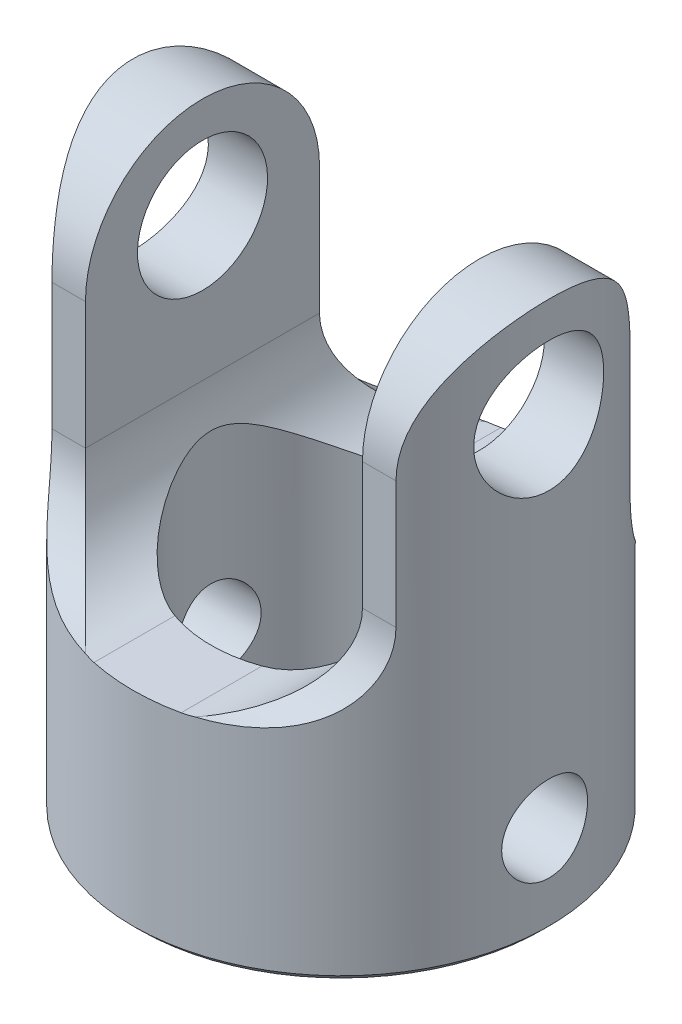
SolidWorks part; units mm, degrees
material "AISI 1045 Steel, cold drawn"
ref_plane "Front Plane" through (0, 0, 0) normal (0, 0, 1) x (1, 0, 0)
ref_plane "Top Plane" through (0, 0, 0) normal (0, 1, 0) x (1, 0, 0)
ref_plane "Right Plane" through (0, 0, 0) normal (1, 0, 0) x (0, 0, -1)
sketch "Sketch1" plane through (0, 0, 0) normal (0, 1, 0) x (1, 0, 0)
  circle A0 centre (0, 0) radius 8
  circle A1 centre (0, 0) radius 5
  dimension "D1" = 16
  dimension "D2" = 10
extrude "Boss-Extrude2" add sketch "Sketch1" along normal mid plane 25
sketch "Sketch3" plane through (0, 0, 0) normal (0, 0, 1) x (1, 0, 0)
  line L1 (-5.325, 13.5) -> (5.325, 13.5)
  line L2 (-5.325, 13.5) -> (-5.325, -4.4)
  line L3 (-5.325, -4.4) -> (5.325, -4.4)
  line L4 (5.325, 13.5) -> (5.325, -4.4)
  line L5 (-5.325, 13.5) -> (5.325, -4.4) construction
  line L6 (-5.325, -4.4) -> (5.325, 13.5) construction
  line L7 (-8, -12.5) -> (8, -12.5) construction
  line L8 (8, 12.5) -> (-8, 12.5) construction
  point P0 (0, 4.55)
  dimension "D1" = 10.65
  dimension "D2" = 8.1
  dimension "D3" = 1
extrude "Cut-Extrude1" cut sketch "Sketch3" against normal through all both and the other way through all
sketch "Sketch4" plane through (0, 0, 0) normal (1, 0, 0) x (0, 0, -1)
  line L0 (-4.5, -4.4) -> (-4.5, 4.13)
  line L1 (4.5, -4.4) -> (4.5, 4.13)
  line L2 (-5, -12.5) -> (5, -12.5) construction
  line L3 (4.5, -4.4) -> (5.9703, -4.4)
  line L5 (-5.9703, -4.4) -> (5.9703, -4.4)
  line L7 (5.9703, -4.4) -> (5.9703, 12.5)
  line L8 (5.9703, 12.5) -> (-5.9703, 12.5)
  line L9 (-5.9703, 12.5) -> (-5.9703, -4.4)
  line L10 (-5.9703, -4.4) -> (-4.5, -4.4)
  line L12 (5.9703, -4.4) -> (5.9703, 12.5)
  line L13 (5.9703, 12.5) -> (-5.9703, 12.5)
  line L14 (-5.9703, 12.5) -> (-5.9703, -4.4)
  arc A0 (-4.5, 4.13) -> (4.5, 4.13) centre (0, 4.13) cw
  dimension "D4" = 16.63
  dimension "D2" = 4.5
  dimension "D3" = 4.5
  dimension "D1" = 0
extrude "Cut-Extrude3" cut sketch "Sketch4" against normal through all both and the other way through all
fillet "Fillet10" radius 3.65 4 edges at (-5.9697, -4.4, -4.5) (5.9697, -4.4, -4.5) (5.9697, -4.4, 4.5) (-5.9697, -4.4, 4.5)
fillet "Fillet11" radius 3.65 2 edges at (5.325, -4.4, 0) (-5.325, -4.4, 0)
ref_plane "Plane1" through (8, 0, 0) normal (1, 0, 0) x (0, 0, -1)
ref_plane "Plane2" through (-8, 0, 0) normal (-1, 0, 0) x (0, 0, 1)
sketch "Sketch5" plane through (8, 0, 0) normal (1, 0, 0) x (0, 0, -1)
  line L0 (-8, -12.5) -> (8, -12.5) construction
  point P0 (0, -9)
  dimension "D1" = 3.5
sketch "Sketch7" plane through (-8, 0, 0) normal (-1, 0, 0) x (0, 0, 1)
  point P0 (0, -9)
hole_wizard "Ø3.3 (3.3) Diameter Hole1" positions "Sketch8" profile "Sketch9" hole size "Ø3.3" standard "ANSI Metric" end condition up to next
sketch "Sketch8" plane through (-8, 0, 0) normal (-1, 0, 0) x (0, 0, 1)
  point P0 (0, -9)
sketch "Sketch9" plane through (-8, -9, 0) normal (0, 1, 0) x (0, 0, 1)
  line L0 (0, 0) -> (0, 3)
  line L1 (0, 3) -> (1.65, 3)
  line L2 (1.65, 3) -> (1.65, 0)
  line L5 (1.65, 0) -> (0, 0)
  line L11 (0, -6.35) -> (0, 107.95) construction
  dimension "Thru Hole Dia." = 3.3
  dimension "Thru Hole Depth" = 3
hole_wizard "Ø3.3 (3.3) Diameter Hole2" positions "Sketch10" profile "Sketch11" hole size "Ø3.3" standard "ANSI Metric" end condition up to next
sketch "Sketch10" plane through (8, 0, 0) normal (1, 0, 0) x (0, 0, -1)
  point P0 (0, -9)
sketch "Sketch11" plane through (8, -9, 0) normal (0, 1, 0) x (0, 0, -1)
  line L0 (0, 0) -> (0, 3)
  line L1 (0, 3) -> (1.65, 3)
  line L2 (1.65, 3) -> (1.65, 0)
  line L5 (1.65, 0) -> (0, 0)
  line L11 (0, -6.35) -> (0, 107.95) construction
  dimension "Thru Hole Dia." = 3.3
  dimension "Thru Hole Depth" = 3
sketch "Sketch12" plane through (0, 0, 0) normal (1, 0, 0) x (0, 0, -1)
  line L0 (-8, -12.5) -> (8, -12.5) construction
  circle A0 centre (0, 4.75) radius 2.5
  dimension "D1" = 5
  dimension "D2" = 17.25
extrude "Cut-Extrude4" cut sketch "Sketch12" against normal through all both and the other way through all
chamfer "Chamfer1" distance 0.25 angle 45 2 edges at (0, -12.5, 5) (0, -12.5, 8)
